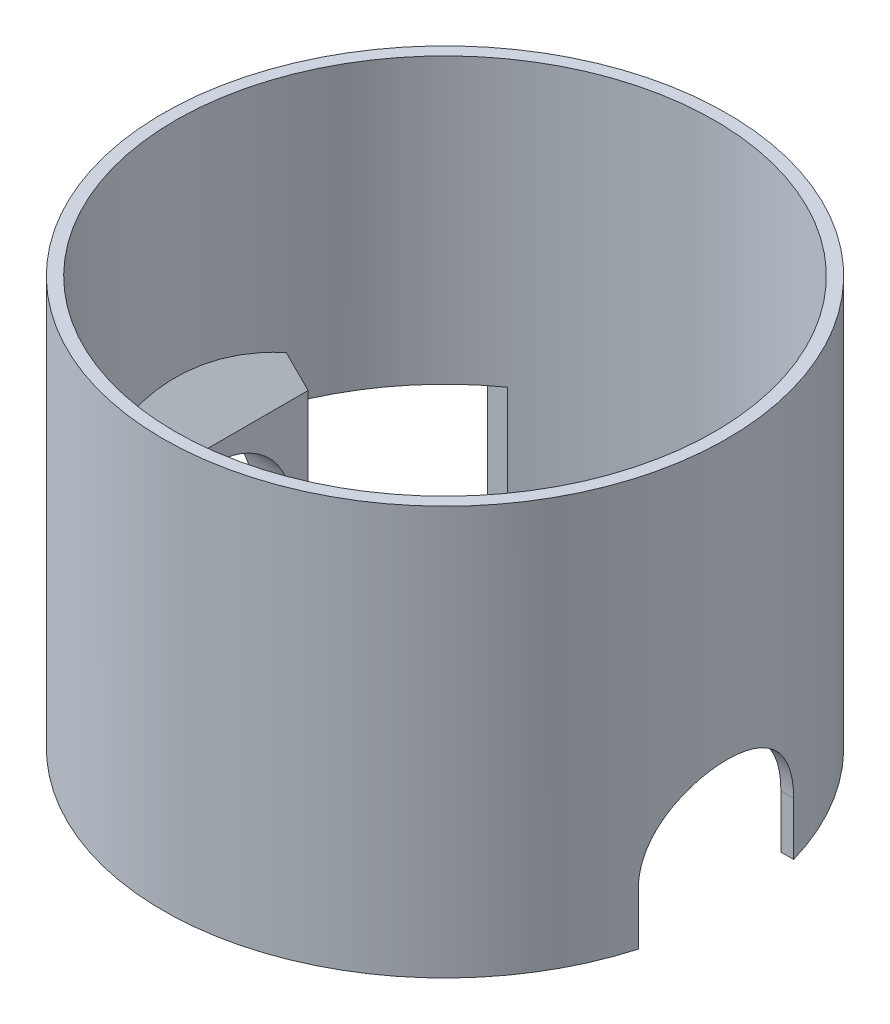
SolidWorks part; units mm, degrees
ref_plane "Front Plane" through (0, 0, 0) normal (0, 0, 1) x (1, 0, 0)
ref_plane "Top Plane" through (0, 0, 0) normal (0, 1, 0) x (1, 0, 0)
ref_plane "Right Plane" through (0, 0, 0) normal (1, 0, 0) x (0, 0, -1)
sketch "Sketch1" plane through (0, 0, 0) normal (0, 1, 0) x (1, 0, 0)
  circle A0 centre (0, 0) radius 69
  circle A1 centre (0, 0) radius 66
  dimension "D1" = 138
  dimension "D2" = 3
extrude "Boss-Extrude1" add sketch "Sketch1" along normal blind 100
sketch "Sketch2" plane through (0, 0, 0) normal (0, 1, 0) x (1, 0, 0)
  line L0 (0, 0) -> (-101.9987, 0) construction
  line L1 (0, 0) -> (-90.6575, -52.3411) construction
  line L2 (-64.9519, -37.5) -> (-82.6631, -6.8233) construction
  dimension "D1" = 30
  dimension "D2" = 75
ref_plane "Plane1" through (-64.9519, 0, 37.5) normal (0.866, 0, -0.5) x (-0.5, 0, -0.866)
sketch "Sketch3" plane through (-64.9519, 0, 37.5) normal (0.866, 0, -0.5) x (-0.5, 0, -0.866)
  line L0 (10, 31.5) -> (10, 59.5)
  line L1 (10, 59.5) -> (-10, 59.5)
  line L2 (-10, 59.5) -> (-10, 31.5)
  line L3 (-10, 31.5) -> (10, 31.5)
  point P2 (0, 31.5)
  dimension "D1" = 20
  dimension "D2" = 31.5
  dimension "D3" = 28
  dimension "D4" = 0
extrude "Cut-Extrude1" cut sketch "Sketch3" along normal up to next
fillet "Fillet1" radius 3 4 edges at (-52.8113, 31.5, 42.0376) (-62.8113, 31.5, 24.7171) (-52.8113, 59.5, 42.0376) (-62.8113, 59.5, 24.7171)
sketch "Sketch4" plane through (0, 0, 0) normal (1, 0, 0) x (0, 0, -1)
  line L1 (23.3, 0) -> (53.7, 0)
  line L2 (23.3, 0) -> (23.3, 30.4)
  line L3 (23.3, 30.4) -> (53.7, 30.4)
  line L4 (53.7, 0) -> (53.7, 30.4)
  dimension "D1" = 30.4
  dimension "D2" = 30.4
  dimension "D3" = 0
  dimension "D4" = 23.3
extrude "Cut-Extrude2" cut sketch "Sketch4" against normal through all
sketch "Sketch5" plane through (0, 0, 0) normal (1, 0, 0) x (0, 0, -1)
  line L8 (19, 13) -> (19, -6)
  line L9 (19, -6) -> (-19, -6)
  line L10 (-19, -6) -> (-19, 13)
  arc A1 (19, 13) -> (-19, 13) centre (0, 13) ccw
  dimension "D1" = 19
extrude "Cut-Extrude6" cut sketch "Sketch5" along normal through all both and the other way through all
sketch "Sketch6" plane through (0, 0, 0) normal (1, 0, 0) x (0, 0, -1)
  line L0 (19, 13) -> (19, 0)
  line L2 (-19, 0) -> (-19, 13)
  line L3 (23, 13) -> (23, 0)
  line L4 (-23, 0) -> (-23, 13)
  line L5 (23, 0) -> (19, 0)
  line L6 (-19, 0) -> (-23, 0)
  arc A0 (19, 13) -> (-19, 13) centre (0, 13) ccw
  arc A1 (23, 13) -> (-23, 13) centre (0, 13) ccw
  dimension "D1" = 19
  dimension "D3" = 0
  dimension "D2" = 4
extrude "Boss-Extrude2" add sketch "Sketch6" against normal up to next from offset 56.5 offset against normal yes
sketch "Sketch7" plane through (-56.5, 0, 0) normal (1, 0, 0) x (0, 0, -1)
  line L0 (0, 36) -> (15, 36) construction
  arc A0 (23, 13) -> (-23, 13) centre (0, 13) ccw construction
  dimension "D1" = 15
ref_plane "Plane2" through (-10.25, -10.25, 0) normal (-0.7071, -0.7071, 0) x (0, 0, -1)
sketch "Sketch8" plane through (-10.25, -10.25, 0) normal (-0.7071, -0.7071, 0) x (0, 0, -1)
  line L0 (23, -39.9515) -> (23, -49.1439) construction
  line L1 (-23, -82.9515) -> (23, -82.9515)
  line L2 (-23, -82.9515) -> (-23, -47.9515)
  line L3 (-23, -47.9515) -> (23, -47.9515)
  line L4 (23, -82.9515) -> (23, -47.9515)
  line L5 (-23, -49.1439) -> (-23, -39.9515) construction
  line L6 (19, -39.9515) -> (23, -39.9515) construction
  dimension "D1" = 0
  dimension "D2" = 0
  dimension "D3" = 8
  dimension "D4" = 35
extrude "Boss-Extrude4" add sketch "Sketch8" along normal blind 30 contours L2 L1 L4 L3
sketch "Sketch9" plane through (0, 0, 0) normal (0, -1, 0) x (1, 0, 0)
  line L12 (63.206, 19) -> (66.3325, 19)
  line L13 (-66.3325, 19) -> (-56.5, 19)
  line L14 (-56.5, 19) -> (-56.5, 23)
  line L15 (-56.5, 23) -> (-61.8628, 23)
  line L18 (-56.5, 19) -> (-56.5, 23)
  line L19 (-56.5, 23) -> (-61.8628, 23)
  line L20 (-56.5, 19) -> (-56.5, -19)
  line L24 (-56.5, -19) -> (-66.3325, -19)
  line L25 (-64.947, -23.3) -> (-61.7504, -23.3)
  line L26 (-61.8628, -23) -> (-56.5, -23)
  line L27 (-56.5, -23) -> (-56.5, -19)
  line L30 (-61.8628, -23) -> (-56.5, -23)
  line L31 (-56.5, -23) -> (-56.5, -19)
  arc A6 (66.3325, 19) -> (-66.3325, 19) centre (0, 0) ccw
  arc A7 (63.206, 19) -> (-61.8628, 23) centre (0, 0) ccw
  arc A8 (66.3325, 19) -> (-66.3325, 19) centre (0, 0) ccw
  arc A9 (63.206, 19) -> (-61.8628, 23) centre (0, 0) ccw
  arc A10 (-66.3325, -19) -> (-66.3325, 19) centre (0, 0) ccw
  arc A11 (-61.8628, -23) -> (-61.8628, 23) centre (0, 0) ccw
  arc A12 (-66.3325, -19) -> (-64.947, -23.3) centre (0, 0) ccw
  arc A13 (-61.8628, -23) -> (-61.7504, -23.3) centre (0, 0) ccw
  arc A14 (-66.3325, -19) -> (-64.947, -23.3) centre (0, 0) ccw
  arc A15 (-61.8628, -23) -> (-61.7504, -23.3) centre (0, 0) ccw
  circle A16 centre (0, 0) radius 69
  arc A18 (-61.8628, -23) -> (-61.8628, 23) centre (0, 0) ccw
  line M15 (-66.3325, 19) -> (-56.5, 19)
  line M16 (-56.5, 19) -> (-56.5, 23)
  line M17 (-56.5, 23) -> (-61.8628, 23)
  arc M18 (-61.8628, 23) -> (63.206, 19) centre (0, 0) cw
  dimension "D1" = 0
  dimension "D2" = 0
extrude "Cut-Extrude7" cut sketch "Sketch9" against normal through all flip side to cut contours A16
extrude "Cut-Extrude8" cut sketch "Sketch9<3>" against normal through all contours L31 L30 A11 M15 M18 M17 M16 region at (1.7062, 0, 0)
sketch "Sketch9<3>" plane through (0, 0, 0) normal (0, -1, 0) x (1, 0, 0) same geometry as "Sketch9"
extrude "Cut-Extrude9" cut sketch "Sketch5<2>" against normal through all
sketch "Sketch5<2>" plane through (0, 0, 0) normal (1, 0, 0) x (0, 0, -1) same geometry as "Sketch5"
